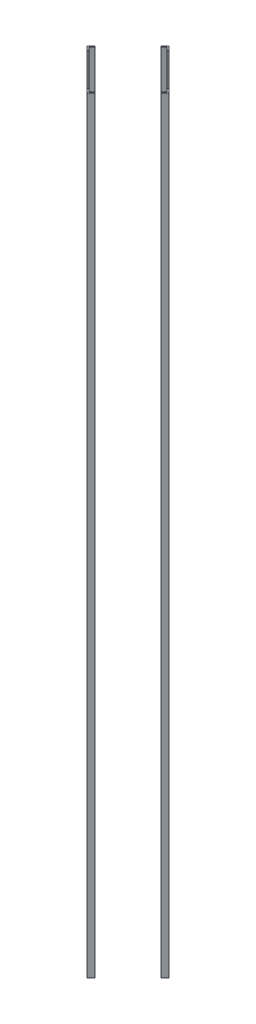
SolidWorks part; units mm, degrees
material "6061-T6 (SS)"
ref_plane "Front Plane" through (0, 0, 0) normal (0, 0, 1) x (1, 0, 0)
ref_plane "Top Plane" through (0, 0, 0) normal (0, 1, 0) x (1, 0, 0)
ref_plane "Right Plane" through (0, 0, 0) normal (1, 0, 0) x (0, 0, -1)
sketch "Sketch2" plane through (0, 0, 0) normal (0, 1, 0) x (1, 0, 0)
  line L0 (0, 94.7743) -> (-8.9803, 85.794)
  line L1 (-8.9803, 85.794) -> (-6.7352, 83.549)
  line L2 (-6.7352, 83.549) -> (0, 90.2842)
  line L3 (0, 90.2842) -> (6.7352, 83.549)
  line L4 (6.7352, 83.549) -> (8.9803, 85.794)
  line L5 (8.9803, 85.794) -> (0, 94.7743)
  line L6 (0, 0) -> (0, 186.644) construction
  line L7 (94.7417, 0.0326) -> (85.7614, 9.0128)
  line L8 (85.7614, 9.0128) -> (83.5164, 6.7678)
  line L9 (83.5164, 6.7678) -> (90.2516, 0.0326)
  line L10 (90.2516, 0.0326) -> (83.5164, -6.7026)
  line L11 (83.5164, -6.7026) -> (85.7614, -8.9477)
  line L12 (85.7614, -8.9477) -> (94.7417, 0.0326)
  line L13 (0, -94.7091) -> (8.9803, -85.7289)
  line L14 (8.9803, -85.7289) -> (6.7352, -83.4838)
  line L15 (6.7352, -83.4838) -> (0, -90.219)
  line L16 (0, -90.219) -> (-6.7352, -83.4838)
  line L17 (-6.7352, -83.4838) -> (-8.9803, -85.7289)
  line L18 (-8.9803, -85.7289) -> (0, -94.7091)
  line L19 (-94.7417, 0.0326) -> (-85.7614, -8.9477)
  line L20 (-85.7614, -8.9477) -> (-83.5164, -6.7026)
  line L21 (-83.5164, -6.7026) -> (-90.2516, 0.0326)
  line L22 (-90.2516, 0.0326) -> (-83.5164, 6.7678)
  line L23 (-83.5164, 6.7678) -> (-85.7614, 9.0128)
  line L24 (-85.7614, 9.0128) -> (-94.7417, 0.0326)
  point P1 (-3.3676, 86.9166)
  point P31 (0, 0.0326)
  dimension "D1" = 127.635
  dimension "D2" = 12.7
  dimension "D3" = 12.7
  dimension "D4" = 3.175
  dimension "D5" = 3.175
  dimension "D7" = 127.635
  dimension "D6" = 4
extrude "Boss-Extrude1" add sketch "Sketch2" along normal blind 1778
sketch "Sketch3" plane through (0, 0, 0) normal (0, -1, 0) x (1, 0, 0)
  circle A0 centre (0, 0) radius 94.7417
